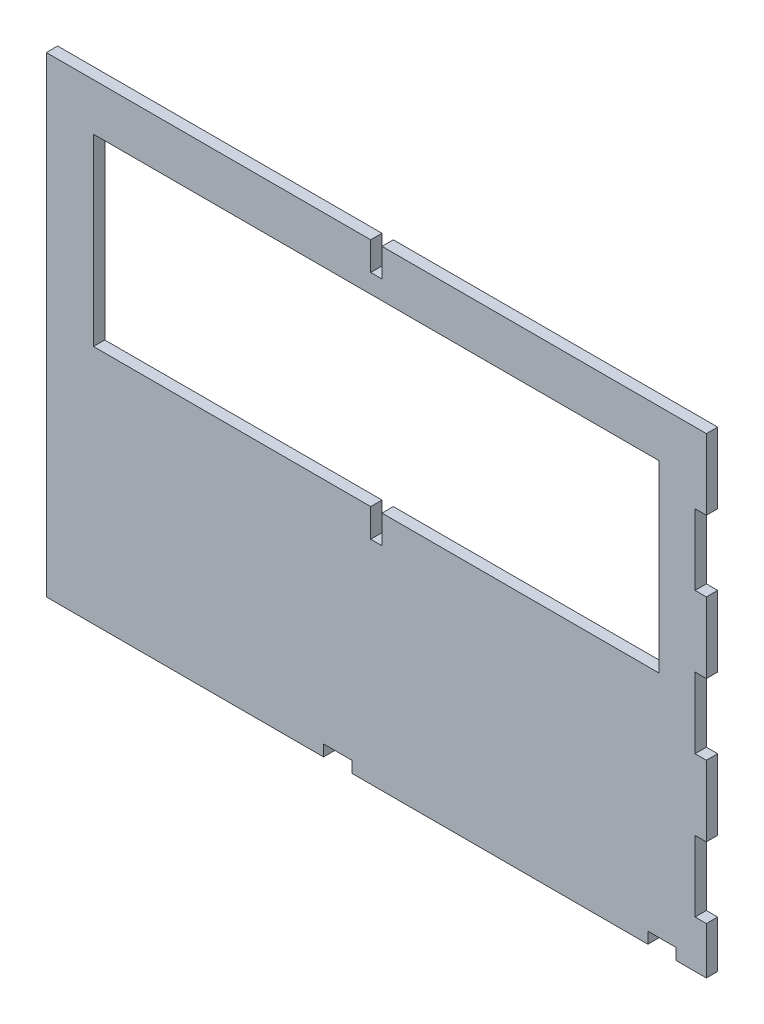
SolidWorks part; units mm, degrees
ref_plane "Front" through (0, 0, 0) normal (0, 0, 1) x (1, 0, 0)
ref_plane "Top" through (0, 0, 0) normal (0, 1, 0) x (1, 0, 0)
ref_plane "Right" through (0, 0, 0) normal (1, 0, 0) x (0, 0, -1)
sketch "Sketch1" plane through (0, 0, 0) normal (0, 0, 1) x (1, 0, 0)
  line L1 (0, 0) -> (-200, 0)
  line L2 (0, 0) -> (0, 150)
  line L4 (-200, 0) -> (-200, 150)
  line L5 (-100, 90) -> (-100, 0) construction
  line L6 (-175, 110) -> (-175, 125)
  line L7 (-25, 110) -> (-25, 125)
  line L9 (-175, 125) -> (-25, 125)
  line L11 (-200, 150) -> (0, 150)
  arc A0 (-153.0972, 57.0313) -> (-46.9028, 57.0312) centre (-100, 90) ccw
  arc A1 (-175, 110) -> (-153.0972, 57.0313) centre (-100, 110) ccw
  arc A2 (-46.9028, 57.0312) -> (-25, 110) centre (-100, 110) ccw
  dimension "D3" = 62.5
  dimension "D4" = 75
  dimension "D1" = 200
  dimension "D2" = 25
  dimension "D5" = 20
  dimension "D6" = 90
  dimension "D7" = 150
extrude "Boss-Extrude1" add sketch "Sketch1" along normal blind 6
sketch "Sketch3" plane through (0, 0, 6) normal (0, 0, 1) x (1, 0, 0)
  line L0 (-200, 150) -> (-200, 0) construction
  line L1 (-100, 27.5) -> (-200, 27.5)
  line L2 (-100, 27.5) -> (-100, 125)
  line L3 (-100, 125) -> (-200, 125)
  line L4 (-200, 27.5) -> (-200, 125)
  line L7 (-25, 125) -> (-175, 125) construction
  arc A0 (-153.0972, 57.0313) -> (-46.9028, 57.0312) centre (-100, 90) ccw construction
extrude "Cut-Extrude1" cut sketch "Sketch3" against normal blind 6
sketch "Sketch4" plane through (0, 0, 6) normal (0, 0, 1) x (1, 0, 0)
  line L0 (-250, 110) -> (-100, 110) construction
  line L1 (-100, 90) -> (-250, 90) construction
  line L2 (-250, 90) -> (-250, 110) construction
  line L3 (-25, 125) -> (0, 125) construction
  line L4 (-200, 27.5) -> (-250, 27.5)
  line L5 (-200, 27.5) -> (-200, 0)
  line L6 (-200, 0) -> (-350, 0)
  line L9 (-350, 0) -> (-350, 150)
  line L11 (-325, 110) -> (-325, 125)
  line L12 (-200, 125) -> (-325, 125)
  line L13 (-200, 125) -> (-200, 150)
  line L14 (-200, 150) -> (-350, 150)
  line L16 (0, 0) -> (0, 150) construction
  line L17 (-325, 125) -> (-350, 125) construction
  line L18 (-200, 0) -> (0, 0) construction
  arc A0 (-325, 110) -> (-303.0972, 57.0312) centre (-250, 110) ccw
  circle A1 centre (-100, 90) radius 62.5 construction
  circle A2 centre (-100, 110) radius 75 construction
  arc A3 (-46.9028, 57.0312) -> (-25, 110) centre (-100, 110) ccw construction
  arc A4 (-100, 27.5) -> (-46.9028, 57.0312) centre (-100, 90) ccw construction
  arc A5 (-303.0972, 57.0312) -> (-250, 27.5) centre (-250, 90) ccw
  dimension "D1" = 150
  dimension "D2" = 125
  dimension "D4" = 125
  dimension "D3" = 150
extrude "Boss-Extrude3" add sketch "Sketch4" against normal blind 6
sketch "Sketch5" plane through (0, 0, 6) normal (0, 0, 1) x (1, 0, 0)
  line L1 (-178, 150) -> (-172, 150)
  line L2 (-178, 150) -> (-178, 135)
  line L3 (-178, 135) -> (-172, 135)
  line L4 (-172, 150) -> (-172, 135)
  line L5 (-250, 27.5) -> (-100, 27.5) construction
  line L6 (-178, 27.5) -> (-172, 27.5)
  line L7 (-178, 27.5) -> (-178, 12.5)
  line L8 (-178, 12.5) -> (-172, 12.5)
  line L9 (-172, 27.5) -> (-172, 12.5)
  line L10 (0, 150) -> (-350, 150) construction
  point P12 (-175, 150)
  point P14 (-175, 150)
  dimension "D1" = 6
  dimension "D2" = 15
extrude "Cut-Extrude2" cut sketch "Sketch5" against normal blind 6
sketch "Sketch6" plane through (0, 0, 6) normal (0, 0, 1) x (1, 0, 0)
  line L0 (0, 0) -> (0, 150) construction
  line L1 (0, 112.5) -> (-6, 112.5)
  line L2 (0, 112.5) -> (0, 75)
  line L3 (0, 75) -> (-6, 75)
  line L4 (-6, 112.5) -> (-6, 75)
  line L5 (0, 150) -> (-172, 150) construction
  dimension "D1" = 37.5
  dimension "6" = 6
  dimension "D2" = 37.5
extrude "Cut-Extrude3" cut sketch "Sketch6" against normal blind 6
sketch "Sketch8" plane through (0, 0, 6) normal (0, 0, 1) x (1, 0, 0)
  line L1 (-350, 0) -> (0, 0)
  line L2 (-350, 0) -> (-350, -100)
  line L3 (-350, -100) -> (0, -100)
  line L4 (0, 0) -> (0, -100)
  dimension "D1" = 100
extrude "Boss-Extrude4" add sketch "Sketch8" against normal up to surface (6 mm away) up to face at (-117.6667, 103.75, 0)
pattern_linear "LPattern1" count 3 spacing 75 along (0, -1, 0) of "Cut-Extrude3"
sketch "Sketch7" plane through (0, 0, 6) normal (0, 0, 1) x (1, 0, 0)
  line L1 (-16, -100) -> (-31, -100)
  line L2 (-16, -100) -> (-16, -94)
  line L3 (-16, -94) -> (-31, -94)
  line L4 (-31, -100) -> (-31, -94)
  line L5 (-6, -37.5) -> (-6, -75) construction
  line L6 (-350, -100) -> (0, -100) construction
  line L7 (-178, 27.5) -> (-178, 12.5) construction
  line L8 (-188, -100) -> (-203, -100)
  line L9 (-188, -100) -> (-188, -94)
  line L10 (-188, -94) -> (-203, -94)
  line L11 (-203, -100) -> (-203, -94)
  dimension "D1" = 15
  dimension "D2" = 10
  dimension "D3" = 6
  dimension "D4" = 10
extrude "s" cut sketch "Sketch7" against normal through all
sketch "Sketch9" plane through (0, 0, 6) normal (0, 0, 1) x (1, 0, 0)
  line L0 (-25, 110) -> (-25, 125) construction
  line L1 (-325, 125) -> (-25, 125)
  line L2 (-325, 125) -> (-325, 27.5)
  line L3 (-325, 27.5) -> (-25, 27.5)
  line L4 (-25, 125) -> (-25, 27.5)
  line L5 (-250, 27.5) -> (-178, 27.5) construction
extrude "Cut-Extrude4" cut sketch "Sketch9" against normal through all
